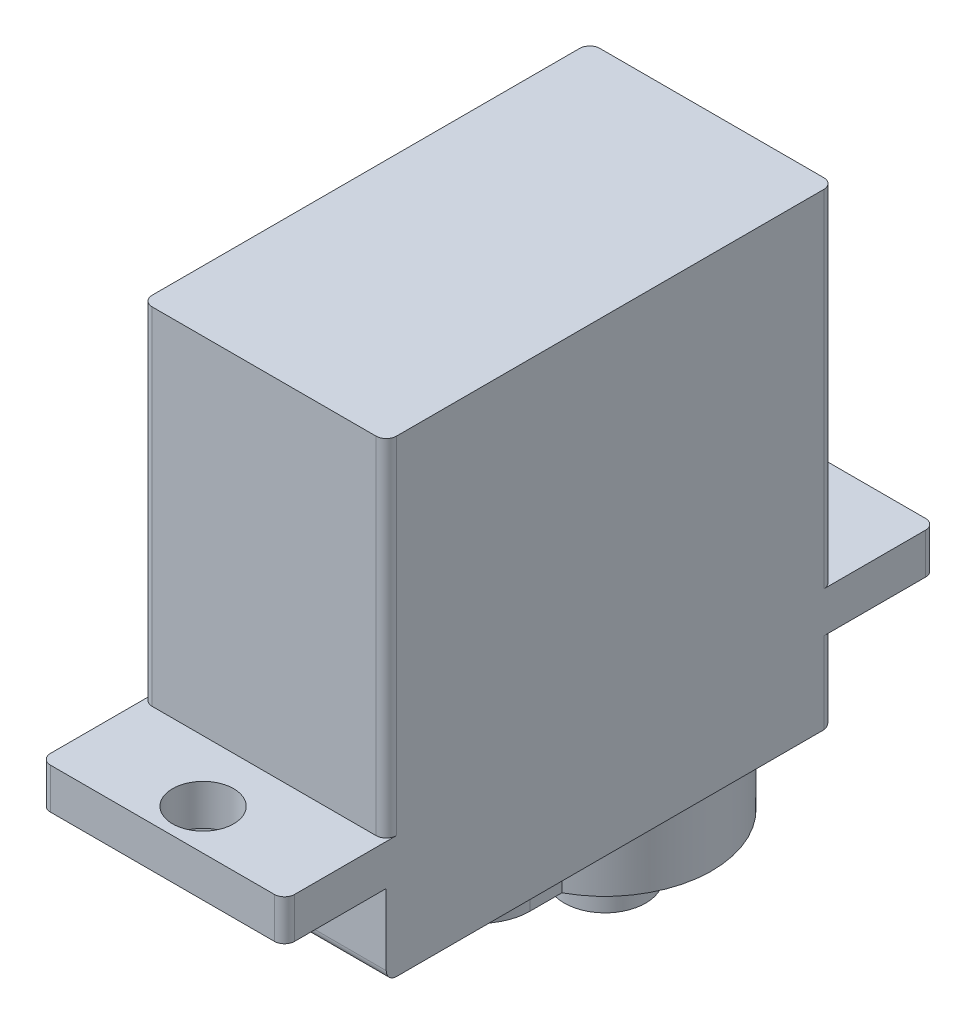
SolidWorks part; units mm, degrees
ref_plane "前视基准面" through (0, 0, 0) normal (0, 0, 1) x (1, 0, 0)
ref_plane "上视基准面" through (0, 0, 0) normal (0, 1, 0) x (1, 0, 0)
ref_plane "右视基准面" through (0, 0, 0) normal (1, 0, 0) x (0, 0, -1)
sketch "草图1" plane through (0, 0, 0) normal (0, 1, 0) x (1, 0, 0)
  circle A0 centre (0, 0) radius 2
  circle A1 centre (0, 0) radius 0.5
extrude "凸台-拉伸1" add sketch "草图1" along normal blind 3
sketch "草图2" plane through (0, 3, 0) normal (0, 1, 0) x (1, 0, 0)
  line L0 (-2.5, -6.189) -> (-2.5, -4.6165)
  line L1 (2.5, -6.189) -> (2.5, -4.6165)
  arc A0 (2.5, -4.6165) -> (-2.5, -4.6165) centre (0, 0) ccw
  arc A1 (-2.5, -6.189) -> (2.5, -6.189) centre (0, -6.189) ccw
  dimension "D1" = 5.25
extrude "凸台-拉伸2" add sketch "草图2" along normal blind 4
sketch "草图3" plane through (0, 7, 0) normal (0, 1, 0) x (1, 0, 0)
  line L1 (-6, 5.25) -> (6, 5.25)
  line L2 (-6, 5.25) -> (-6, -16.75)
  line L3 (-6, -16.75) -> (6, -16.75)
  line L4 (6, 5.25) -> (6, -16.75)
  point P4 (0, 5.25)
  dimension "D1" = 12
  dimension "D2" = 5.25
  dimension "D3" = 6
  dimension "D4" = 22
extrude "凸台-拉伸3" add sketch "草图3" along normal blind 4
sketch "草图4" plane through (0, 11, 0) normal (0, 1, 0) x (1, 0, 0)
  line L0 (6, 5.25) -> (-6, 5.25) construction
  line L1 (-6, 10.25) -> (6, 10.25)
  line L2 (-6, 10.25) -> (-6, -21.75)
  line L3 (-6, -21.75) -> (6, -21.75)
  line L4 (6, 10.25) -> (6, -21.75)
  line L5 (-6.9229, -5.75) -> (15.3507, -5.75) construction
  circle A0 centre (0, 8.25) radius 1.5
  circle A1 centre (0, -19.75) radius 1.5
  dimension "D5" = 3
  dimension "D1" = 32
  dimension "D2" = 5
  dimension "D3" = 12
  dimension "D4" = 3
extrude "凸台-拉伸4" add sketch "草图4" along normal blind 2
sketch "草图5" plane through (0, 13, 0) normal (0, 1, 0) x (1, 0, 0)
  line L0 (-6, 10.25) -> (-6, -21.75) construction
  line L1 (-6, 5.25) -> (6, 5.25)
  line L2 (-6, 5.25) -> (-6, -16.75)
  line L3 (-6, -16.75) -> (6, -16.75)
  line L4 (6, 5.25) -> (6, -16.75)
  line L5 (6, -21.75) -> (6, 10.25) construction
  dimension "D1" = 22
  dimension "D2" = 5
extrude "凸台-拉伸5" add sketch "草图5" along normal blind 17
fillet "圆角1" radius 0.5 12 edges at (3, 7, -5.25) (-3, 7, -5.25) (-6, 21.5, -5.25) (-6, 21.5, 16.75) (6, 21.5, 16.75) (0, 7, 16.75) (6, 21.5, -5.25) (6, 9, -5.25) (6, 12, -10.25) (-6, 12, -10.25) (-6, 12, 21.75) (6, 12, 21.75)
